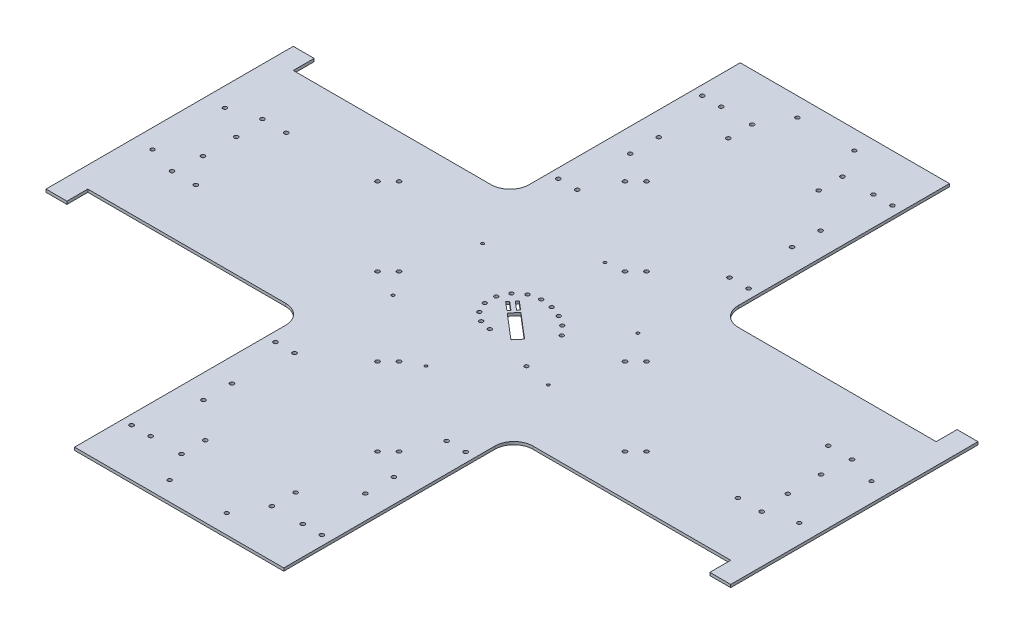
SolidWorks part; units mm, degrees
ref_plane "Front Plane" through (0, 0, 0) normal (0, 0, 1) x (1, 0, 0)
ref_plane "Top Plane" through (0, 0, 0) normal (0, 1, 0) x (1, 0, 0)
ref_plane "Right Plane" through (0, 0, 0) normal (1, 0, 0) x (0, 0, -1)
sketch "Sketch1" plane through (0, 0, 0) normal (0, 1, 0) x (1, 0, 0)
  line L0 (-110, 350) -> (-110, 108)
  line L1 (-110, 108) -> (-338, 108)
  line L2 (-338, 108) -> (-338, 130)
  line L3 (-338, 130) -> (-360, 130)
  line L4 (-360, 130) -> (-360, -130)
  line L5 (-360, 0) -> (1003.1457, 0) construction
  line L6 (0, 350) -> (0, -620.7989) construction
  line L7 (-338, -130) -> (-360, -130)
  line L8 (-338, -108) -> (-338, -130)
  line L9 (-110, -108) -> (-338, -108)
  line L10 (-110, 350) -> (110, 350)
  line L11 (-110, -350) -> (-110, -108)
  line L12 (-110, -350) -> (110, -350)
  line L13 (110, -350) -> (110, -108)
  line L14 (110, -108) -> (338, -108)
  line L15 (338, -108) -> (338, -130)
  line L16 (338, -130) -> (360, -130)
  line L17 (360, 130) -> (360, -130)
  line L18 (338, 130) -> (360, 130)
  line L19 (338, 108) -> (338, 130)
  line L20 (110, 108) -> (338, 108)
  line L21 (110, 350) -> (110, 108)
  point P17 (0, -350)
  dimension "D1" = 110
  dimension "D2" = 22
  dimension "D3" = 22
  dimension "D4" = 242
  dimension "D5" = 130
  dimension "D6" = 250
  dimension "D7" = 110
  dimension "D8" = 108
extrude "Boss-Extrude1" add sketch "Sketch1" along normal blind 3
sketch "Sketch2" plane through (0, 3, 0) normal (0, 1, 0) x (1, 0, 0)
  line L0 (360, -130) -> (360, 130) construction
  line L2 (338, 108) -> (110, 108) construction
  line L4 (0, 107.9437) -> (0, -458.275) construction
  line L5 (110, 108) -> (110, 350) construction
  line L6 (110, 350) -> (-110, 350) construction
  line L7 (-540.1841, 0) -> (-80.3508, 0) construction
  circle A0 centre (310, 47.5) radius 2.125
  circle A1 centre (285, 47.5) radius 2.125
  circle A2 centre (307.5, 17.5) radius 2.125
  circle A3 centre (307.5, -17.5) radius 2.125
  circle A4 centre (310, -47.5) radius 2.125
  circle A5 centre (285, -47.5) radius 2.125
  circle A6 centre (-285, -47.5) radius 2.125
  circle A7 centre (-310, -47.5) radius 2.125
  circle A8 centre (-307.5, -17.5) radius 2.125
  circle A9 centre (-307.5, 17.5) radius 2.125
  circle A10 centre (-285, 47.5) radius 2.125
  circle A11 centre (-310, 47.5) radius 2.125
  circle A13 centre (47.5, 300) radius 2.125
  circle A15 centre (47.5, 275) radius 2.125
  circle A16 centre (-47.5, 275) radius 2.125
  circle A17 centre (-47.5, 300) radius 2.125
  circle A18 centre (-47.5, -300) radius 2.125
  circle A19 centre (-47.5, -275) radius 2.125
  circle A20 centre (47.5, -275) radius 2.125
  circle A21 centre (47.5, -300) radius 2.125
  dimension "D1" = 4.25
  dimension "D2" = 4.25
  dimension "D3" = 4.25
  dimension "D4" = 4.25
  dimension "D5" = 4.25
  dimension "D6" = 4.25
  dimension "D15" = 4.25
  dimension "D16" = 4.25
  dimension "D7" = 50
  dimension "D8" = 25
  dimension "D9" = 95
  dimension "D10" = 35
  dimension "D11" = 60.5
  dimension "D12" = 90.5
  dimension "D13" = 52.5
  dimension "D14" = 110
  dimension "D17" = 50
  dimension "D18" = 25
  dimension "D19" = 62.5
  dimension "D20" = 108
extrude "Cut-Extrude1" cut sketch "Sketch2" against normal through all
sketch "Sketch3" plane through (0, 3, 0) normal (0, 1, 0) x (1, 0, 0)
  line L0 (360, -130) -> (360, 130) construction
  line L1 (338, 108) -> (110, 108) construction
  line L2 (-553.4456, 0) -> (-91.4299, 0) construction
  line L3 (0, 286.895) -> (0, -255.8046) construction
  line L4 (110, 108) -> (110, 350) construction
  line L5 (110, 350) -> (-110, 350) construction
  line L6 (-110, 350) -> (-110, 108) construction
  circle A0 centre (340, 38) radius 2
  circle A2 centre (340, -38) radius 2
  circle A3 centre (-340, -38) radius 2
  circle A4 centre (-340, 38) radius 2
  circle A5 centre (-30, 330) radius 2
  circle A7 centre (30, 330) radius 2
  circle A8 centre (30, -330) radius 2
  circle A9 centre (-30, -330) radius 2
  dimension "D1" = 4
  dimension "D6" = 4
  dimension "D7" = 80
  dimension "D2" = 20
  dimension "D3" = 70
  dimension "D4" = 108
  dimension "D5" = 110
  dimension "D8" = 20
extrude "Cut-Extrude2" cut sketch "Sketch3" against normal through all
sketch "Sketch4" plane through (0, 3, 0) normal (0, 1, 0) x (1, 0, 0)
  line L0 (0.8085, 29.8301) -> (-10.8593, 27.1789) construction
  line L1 (-10.8593, 27.1789) -> (-20.2814, 19.6888) construction
  line L2 (-20.2814, 19.6888) -> (-25.5122, 8.8484) construction
  line L3 (-25.5122, 8.8484) -> (-25.5122, -3.1881) construction
  line L4 (-25.5122, -3.1881) -> (-20.2814, -14.0285) construction
  line L5 (-20.2814, -14.0285) -> (-10.8593, -21.5186) construction
  line L6 (-10.8593, -21.5186) -> (0.8815, -24.1698) construction
  line L7 (0.8085, 29.8301) -> (13.3461, 28.3304) construction
  line L8 (13.3461, 28.3304) -> (25.203, 23.9881) construction
  line L9 (25.203, 23.9881) -> (35.7602, 17.0608) construction
  line L10 (35.7602, 17.0608) -> (44.4635, 7.9124) construction
  line L11 (44.4635, 7.9124) -> (53.9283, -38.7532) construction
  line L12 (0.8085, 2.8301) -> (0.8085, 97.0801) construction
  line L13 (0.8085, 2.8301) -> (0.8085, 97.0801) construction
  line L14 (0.8085, 2.8301) -> (82.4314, 49.9551) construction
  line L15 (-4.5918, -0.4234) -> (21.6669, -22.8005)
  line L16 (21.6669, -22.8005) -> (28.2827, -15.037)
  line L17 (-4.5918, -0.4234) -> (2.0241, 7.3401)
  line L18 (2.0241, 7.3401) -> (28.2827, -15.037)
  line L19 (-6.8751, 1.5225) -> (-4.9293, 3.8058)
  line L20 (-4.9293, 3.8058) -> (-14.0627, 11.5892)
  line L21 (-14.0627, 11.5892) -> (-16.0085, 9.3058)
  line L22 (-16.0085, 9.3058) -> (-6.8751, 1.5225)
  line L23 (2.0241, 7.3401) -> (0.8085, 2.8301) construction
  line L24 (-2.2051, 7.0025) -> (-0.2593, 9.2859)
  line L25 (-0.2593, 9.2859) -> (-9.3927, 17.0692)
  line L26 (-9.3927, 17.0692) -> (-11.3385, 14.7859)
  line L27 (-11.3385, 14.7859) -> (-2.2051, 7.0025)
  line L28 (0.8085, 2.8301) -> (48.4037, 2.8301) construction
  line L29 (0.8085, 2.8301) -> (0.8085, -17.1699) construction
  circle A0 centre (0.8085, 29.8301) radius 2
  circle A1 centre (13.3461, 28.3304) radius 2
  circle A2 centre (25.203, 23.9881) radius 2
  circle A3 centre (35.7602, 17.0608) radius 2
  circle A4 centre (44.4635, 7.9124) radius 2
  circle A5 centre (53.9283, -38.7532) radius 2
  circle A6 centre (0.8085, 2.8301) radius 135 construction
  circle A7 centre (-10.8593, 27.1789) radius 2
  circle A8 centre (-20.2814, 19.6888) radius 2
  circle A9 centre (-25.5122, 8.8484) radius 2
  circle A10 centre (-25.5122, -3.1881) radius 2
  circle A11 centre (-20.2814, -14.0285) radius 2
  circle A12 centre (-10.8593, -21.5186) radius 2
  circle A13 centre (0.8815, -24.1698) radius 2
  circle A14 centre (0.8085, 2.8301) radius 27 construction
  circle A15 centre (0.8085, 2.8301) radius 28.4158 construction
  circle A16 centre (0.8085, 2.8301) radius 32.2916 construction
  circle A17 centre (0.8085, 2.8301) radius 37.7377 construction
  circle A18 centre (0.8085, 2.8301) radius 43.9498 construction
  circle A19 centre (0.8085, 2.8301) radius 67.4602 construction
  circle A20 centre (0.8085, 2.8301) radius 94.25 construction
  circle A21 centre (0.8085, 97.0801) radius 1.5
  circle A22 centre (82.4314, 49.9551) radius 1.5
  circle A23 centre (82.4314, -44.2949) radius 1.5
  circle A24 centre (0.8085, -91.4199) radius 1.5
  circle A25 centre (-80.8144, -44.2949) radius 1.5
  circle A26 centre (-80.8144, 49.9551) radius 1.5
  point P32 (0.8085, 2.8301)
  dimension "D1" = 4
  dimension "D2" = 270
  dimension "D3" = 54
  dimension "D12" = 188.5
  dimension "D13" = 3
  dimension "D4" = 11.9653
  dimension "D5" = 12.627
  dimension "D6" = 47.6157
  dimension "D8" = 60.7074
  dimension "D9" = 70.0293
  dimension "D10" = 81.6875
  dimension "D14" = 60
  dimension "D15" = 34.5
  dimension "D16" = 10.2
  dimension "D17" = 12
  dimension "D18" = 3
  dimension "D19" = 3
  dimension "D20" = 4.6709
  dimension "D21" = 3
  dimension "D22" = 20
  dimension "D23" = 130.437
  dimension "D24" = 5.4003
extrude "Cut-Extrude3" cut sketch "Sketch4" against normal blind 10
sketch "Sketch5" plane through (0, 3, 0) normal (0, 1, 0) x (1, 0, 0)
  line L0 (110, 350) -> (-110, 350) construction
  line L1 (110, 108) -> (110, 350) construction
  line L2 (0, 224.365) -> (185.6725, 224.365) construction
  line L3 (90, 361.0488) -> (90, 126.2188) construction
  line L4 (0, 375.894) -> (0, 88.4107) construction
  line L5 (349.7475, 0) -> (-242.2654, 0) construction
  circle A0 centre (80, 300) radius 2.125
  circle A1 centre (80, 148.73) radius 2.125
  circle A2 centre (85.11, 239.365) radius 2.125
  circle A3 centre (85.11, 209.365) radius 2.125
  circle A4 centre (100, 148.73) radius 2.125
  circle A5 centre (100, 300) radius 2.125
  circle A6 centre (-100, 300) radius 2.125
  circle A7 centre (-100, 148.73) radius 2.125
  circle A8 centre (-85.11, 209.365) radius 2.125
  circle A9 centre (-85.11, 239.365) radius 2.125
  circle A10 centre (-80, 148.73) radius 2.125
  circle A11 centre (-80, 300) radius 2.125
  circle A12 centre (-80, -300) radius 2.125
  circle A13 centre (-80, -148.73) radius 2.125
  circle A14 centre (-85.11, -239.365) radius 2.125
  circle A15 centre (-85.11, -209.365) radius 2.125
  circle A16 centre (-100, -148.73) radius 2.125
  circle A17 centre (-100, -300) radius 2.125
  circle A18 centre (100, -300) radius 2.125
  circle A19 centre (100, -148.73) radius 2.125
  circle A20 centre (85.11, -209.365) radius 2.125
  circle A21 centre (85.11, -239.365) radius 2.125
  circle A22 centre (80, -148.73) radius 2.125
  circle A23 centre (80, -300) radius 2.125
  dimension "D1" = 4.25
  dimension "D2" = 4.25
  dimension "D6" = 4.25
  dimension "D7" = 4.25
  dimension "D3" = 151.27
  dimension "D4" = 50
  dimension "30" = 30
  dimension "D5" = 5.11
  dimension "D8" = 30
  dimension "D9" = 75.635
  dimension "D10" = 15
  dimension "D11" = 10
extrude "Cut-Extrude4" cut sketch "Sketch5" against normal blind 10
fillet "Fillet1" radius 20 4 edges at (110, 1.5, -108) (-110, 1.5, -108) (-110, 1.5, 108) (110, 1.5, 108)
sketch "Sketch6" plane through (0, 3, 0) normal (0, 1, 0) x (1, 0, 0)
  line L0 (-327.256, 327.256) -> (0, 0) construction
  line L1 (0, 429.479) -> (0, -412.5125) construction
  line L2 (-249.4214, 108) -> (110, -251.4214) construction
  line L3 (-226.7939, 108) -> (110, -228.7939) construction
  line L4 (327.256, 327.256) -> (0, 0) construction
  line L5 (-244.4559, 114.3482) -> (114.8318, -244.9395) construction
  line L6 (-130, 108) -> (-338, 108) construction
  line L7 (110, -350) -> (110, -128) construction
  circle A0 centre (53.3259, -194.7473) radius 2.125
  circle A1 centre (-192.7473, 51.3259) radius 2.125
  circle A2 centre (-28.6985, -112.7229) radius 2.125
  circle A3 centre (-110.7229, -30.6985) radius 2.125
  circle A4 centre (64.6396, -183.4335) radius 2.125
  circle A5 centre (-17.3848, -101.4092) radius 2.125
  circle A6 centre (-99.4092, -19.3848) radius 2.125
  circle A7 centre (-181.4335, 62.6396) radius 2.125
  circle A8 centre (-62.6396, 181.4335) radius 2.125
  circle A9 centre (19.3848, 99.4092) radius 2.125
  circle A10 centre (101.4092, 17.3848) radius 2.125
  circle A11 centre (183.4335, -64.6396) radius 2.125
  circle A12 centre (30.6985, 110.7229) radius 2.125
  circle A13 centre (112.7229, 28.6985) radius 2.125
  circle A14 centre (-51.3259, 192.7473) radius 2.125
  circle A15 centre (194.7473, -53.3259) radius 2.125
  point P23 (-69.7107, -71.7107)
  point P49 (71.7107, 69.7107)
  dimension "D3" = 4.25
  dimension "D5" = 4.25
  dimension "D8" = 4.25
  dimension "D10" = 4.25
  dimension "D1" = 45
  dimension "D2" = 100
  dimension "D4" = 16
  dimension "D6" = 348
  dimension "D7" = 174
  dimension "D9" = 116
  dimension "D11" = 116
  dimension "D12" = 8
extrude "Cut-Extrude5" cut sketch "Sketch6" against normal through all
equation "\"M3\"= 4.25mm"
equation "\"D1@Sketch2\"=\"M3\""
equation "\"D2@Sketch2\"=\"M3\""
equation "\"D3@Sketch2\"=\"M3\""
equation "\"D4@Sketch2\"=\"M3\""
equation "\"D5@Sketch2\"=\"M3\""
equation "\"D6@Sketch2\"=\"M3\""
equation "\"D15@Sketch2\"=\"M3\""
equation "\"D16@Sketch2\"=\"M3\""
equation "\"D6@Sketch5\"=\"M3\""
equation "\"D7@Sketch5\"=\"M3\""
equation "\"D2@Sketch5\"=\"M3\""
equation "\"D10@Sketch6\"=\"M3\""
equation "\"D3@Sketch6\"=\"M3\""
equation "\"D8@Sketch6\"=\"M3\""
equation "\"D5@Sketch6\"=\"M3\""
